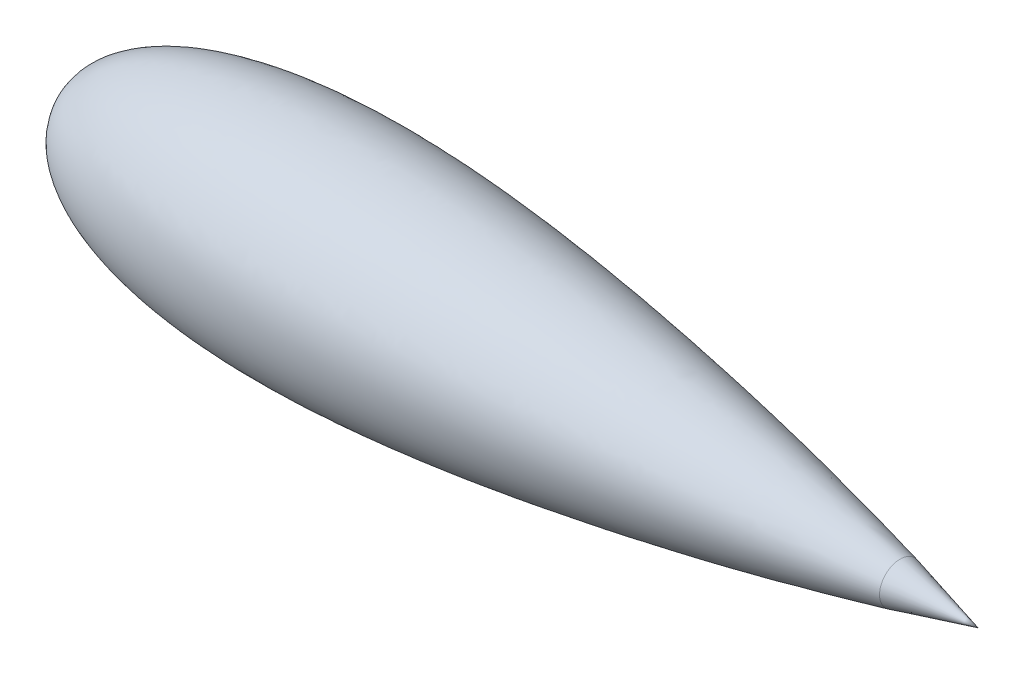
SolidWorks part; units mm, degrees
ref_plane "Front Plane" through (0, 0, 0) normal (0, 0, 1) x (1, 0, 0)
ref_plane "Top Plane" through (0, 0, 0) normal (0, 1, 0) x (1, 0, 0)
ref_plane "Right Plane" through (0, 0, 0) normal (1, 0, 0) x (0, 0, -1)
curve "Curve1"
  spline degree 3 poles (50, 0.1106, 0) (49.1672, 0.3112, 0) (47.504, 0.7118, 0) (44.174, 1.4569, 0) (40.0109, 2.3125, 0) (35.0102, 3.2244, 0) (30.0103, 4.0154, 0) (25.0104, 4.6619, 0) (20.0089, 5.1215, 0) (15.8343, 5.2834, 0) (12.4972, 5.2197, 0) (9.9918, 5.0462, 0) (7.4799, 4.712, 0) (5.3907, 4.2431, 0) (3.726, 3.6886, 0) (2.4481, 3.123, 0) (1.3811, 2.4455, 0) (0.3853, 1.4829, 0) (-0.2566, 0, 0) (0.3853, -1.4829, 0) (1.3811, -2.4455, 0) (2.4481, -3.123, 0) (3.726, -3.6886, 0) (5.3907, -4.2431, 0) (7.4799, -4.712, 0) (9.9918, -5.0462, 0) (12.4972, -5.2197, 0) (15.8343, -5.2834, 0) (20.0089, -5.1215, 0) (25.0104, -4.6619, 0) (30.0103, -4.0154, 0) (35.0102, -3.2244, 0) (40.0109, -2.3125, 0) (44.174, -1.4569, 0) (47.504, -0.7118, 0) (49.1672, -0.3112, 0) (50, -0.1106, 0) knots 0 0 0 0 0.024527 0.048982 0.097703 0.14621 0.194519 0.242629 0.29054 0.33829 0.362156 0.386078 0.410162 0.434658 0.44725 0.460342 0.474624 0.483098 0.5 0.516902 0.525376 0.539658 0.55275 0.565342 0.589838 0.613922 0.637844 0.66171 0.70946 0.757371 0.805481 0.85379 0.902297 0.951018 0.975473 1 1 1 1
sketch "Sketch3" plane through (0, 0, 0) normal (0, 0, 1) x (1, 0, 0)
  line L0 (-1.2, 0) -> (0, 0)
  line L1 (-5.1372, 0) -> (65.0499, 0) construction
  line L2 (55.1191, 0) -> (50.281, 1.2772)
  line L3 (50, 0.1106) -> (50.4537, 0)
  line L4 (50.4537, 0) -> (55.1191, 0)
  spline S0 degree 3 poles (667.8839, 1899.5893) (152.0609, -55.552) (102.5978, -11.6164) (44.174, 1.4569) (40.0109, 2.3125) (35.0102, 3.2244) (30.0103, 4.0154) (25.0104, 4.6619) (20.0089, 5.1215) (15.8343, 5.2834) (12.4972, 5.2197) (9.9918, 5.0462) (7.4799, 4.712) (5.3907, 4.2431) (3.726, 3.6886) (2.4481, 3.123) (1.3811, 2.4455) (0.3853, 1.4829) (-0.2566, 0) (0.3853, -1.4829) (1.3811, -2.4455) (2.4481, -3.123) (3.726, -3.6886) (5.3907, -4.2431) (7.4799, -4.712) (9.9918, -5.0462) (12.4972, -5.2197) (15.8343, -5.2834) (20.0089, -5.1215) (25.0104, -4.6619) (30.0103, -4.0154) (35.0102, -3.2244) (40.0109, -2.3125) (44.174, -1.4569) (102.5977, 11.6164) (152.0607, 55.5518) (667.8797, -1899.5732) knots -1.616456 -1.616456 -1.616456 -1.616456 0.024527 0.048982 0.097703 0.14621 0.194519 0.242629 0.29054 0.33829 0.362156 0.386078 0.410162 0.434658 0.44725 0.460342 0.474624 0.483098 0.5 0.516902 0.525376 0.539658 0.55275 0.565342 0.589838 0.613922 0.637844 0.66171 0.70946 0.757371 0.805481 0.85379 0.902297 0.951018 0.975473 2.616451 2.616451 2.616451 2.616451 only from (50, 0.1106) to (50, -0.1106) construction
  spline S1 degree 3 poles (50, 0.1106) (49.1672, 0.3112) (47.504, 0.7118) (44.174, 1.4569) (40.0109, 2.3125) (35.0102, 3.2244) (30.0103, 4.0154) (25.0104, 4.6619) (20.0089, 5.1215) (15.8343, 5.2834) (12.4972, 5.2197) (9.9918, 5.0462) (7.4799, 4.712) (5.3907, 4.2431) (3.726, 3.6886) (2.4481, 3.123) (1.3811, 2.4455) (0.3853, 1.4829) (0, 0.5928) (0, 0) knots 0 0 0 0 0.024527 0.048982 0.097703 0.14621 0.194519 0.242629 0.29054 0.33829 0.362156 0.386078 0.410162 0.434658 0.44725 0.460342 0.474624 0.483098 0.5 0.5 0.5 0.5
  spline S2 degree 1 poles (50.281, 1.2772) (-1.2, 0) knots 0 0 1 1 construction
  spline S3 degree 3 poles (50.281, 1.2772) (48.1479, 1.791) (43.8706, 2.7738) (37.4079, 4.0327) (30.911, 5.1118) (25.4579, 5.821) (21.0642, 6.2239) (17.7505, 6.4197) (14.4205, 6.4788) (11.0708, 6.3586) (8.2711, 6.053) (6.029, 5.6249) (4.3539, 5.1816) (2.6942, 4.5823) (1.3184, 3.8592) (0.2936, 3.0851) (-0.4635, 2.2875) (-0.9351, 1.4228) (-1.1566, 0.6427) (-1.2, 0.2118) (-1.2, 0) knots 0 0 0 0 0.0625 0.125 0.1875 0.25 0.28125 0.3125 0.34375 0.375 0.40625 0.421875 0.4375 0.453125 0.46875 0.476562 0.484375 0.492188 0.496094 0.5 0.5 0.5 0.5
  dimension "D1" = 1.2
revolve "Revolve2" add sketch "Sketch3" angle 360 about L1
ref_axis "Axis2" through (-7.0056, 0, 0) along (1, 0, 0)
sketch "Sketch5" plane through (0, 0, 0) normal (1, 0, 0) x (0, 0, -1)
  circle A0 centre (0, 0) radius 2.1
  dimension "D1" = 4.2
extrude "Cut-Extrude1" cut sketch "Sketch5" against normal through all and the other way blind 12
ref_plane "Plane2" through (-0.5334, 0, 0) normal (1, 0, 0) x (0, 0, -1)
